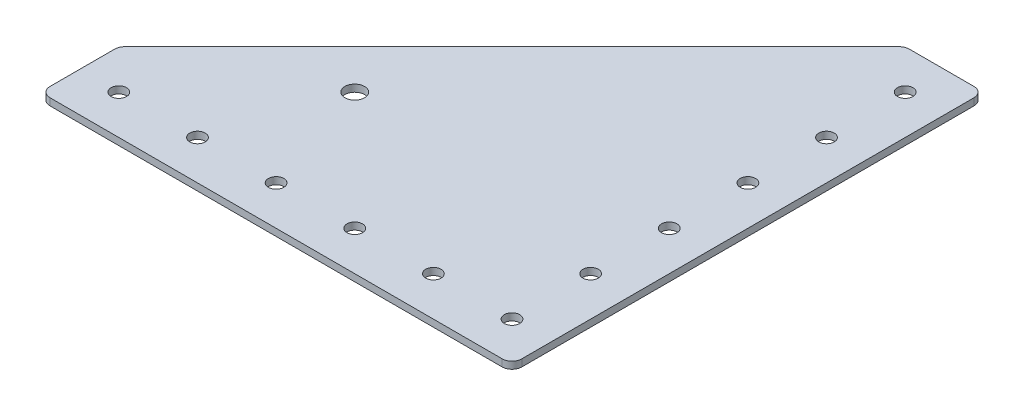
SolidWorks part; units mm, degrees
ref_plane "Front Plane" through (0, 0, 0) normal (0, 0, 1) x (1, 0, 0)
ref_plane "Top Plane" through (0, 0, 0) normal (0, 1, 0) x (1, 0, 0)
ref_plane "Right Plane" through (0, 0, 0) normal (1, 0, 0) x (0, 0, -1)
sketch "Sketch1" plane through (0, 0, 0) normal (0, 1, 0) x (1, 0, 0)
  line L0 (0, 0) -> (0, 152.4)
  line L1 (0, 152.4) -> (-25.4, 152.4)
  line L2 (-25.4, 152.4) -> (-152.4, 25.4)
  line L3 (-152.4, 25.4) -> (-152.4, 0)
  line L4 (-152.4, 0) -> (0, 0)
  circle A0 centre (-12.7, 12.7) radius 2.4892
  circle A1 centre (-38.1, 12.7) radius 2.4892
  circle A2 centre (-63.5, 12.7) radius 2.4892
  circle A3 centre (-88.9, 12.7) radius 2.4892
  circle A4 centre (-114.3, 12.7) radius 2.4892
  circle A5 centre (-12.7, 38.1) radius 2.4892
  circle A6 centre (-12.7, 63.5) radius 2.4892
  circle A7 centre (-12.7, 88.9) radius 2.4892
  circle A8 centre (-12.7, 114.3) radius 2.4892
  circle A9 centre (-139.7, 12.7) radius 2.4892
  circle A13 centre (-12.7, 139.7) radius 2.4892
  circle A17 centre (-101.6, 50.8) radius 3.175
  dimension "D4" = 12.7
  dimension "D5" = 12.7
  dimension "D11" = 6.35
  dimension "D12" = 4.9784
  dimension "D1" = 152.4
  dimension "D2" = 25.4
  dimension "D3" = 152.4
  dimension "D8" = 101.6
  dimension "D9" = 50.8
  dimension "D10" = 25.4
  dimension "D6" = 6
  dimension "D7" = 6
extrude "Boss-Extrude2" add sketch "Sketch1" along normal mid plane 2.286
fillet "Fillet1" radius 3.175 2 edges at (0, 0, 0) (-152.4, 0, 0)
fillet "Fillet2" radius 3.175 3 edges at (-152.4, 0, -25.4) (-25.4, 0, -152.4) (0, 0, -152.4)
